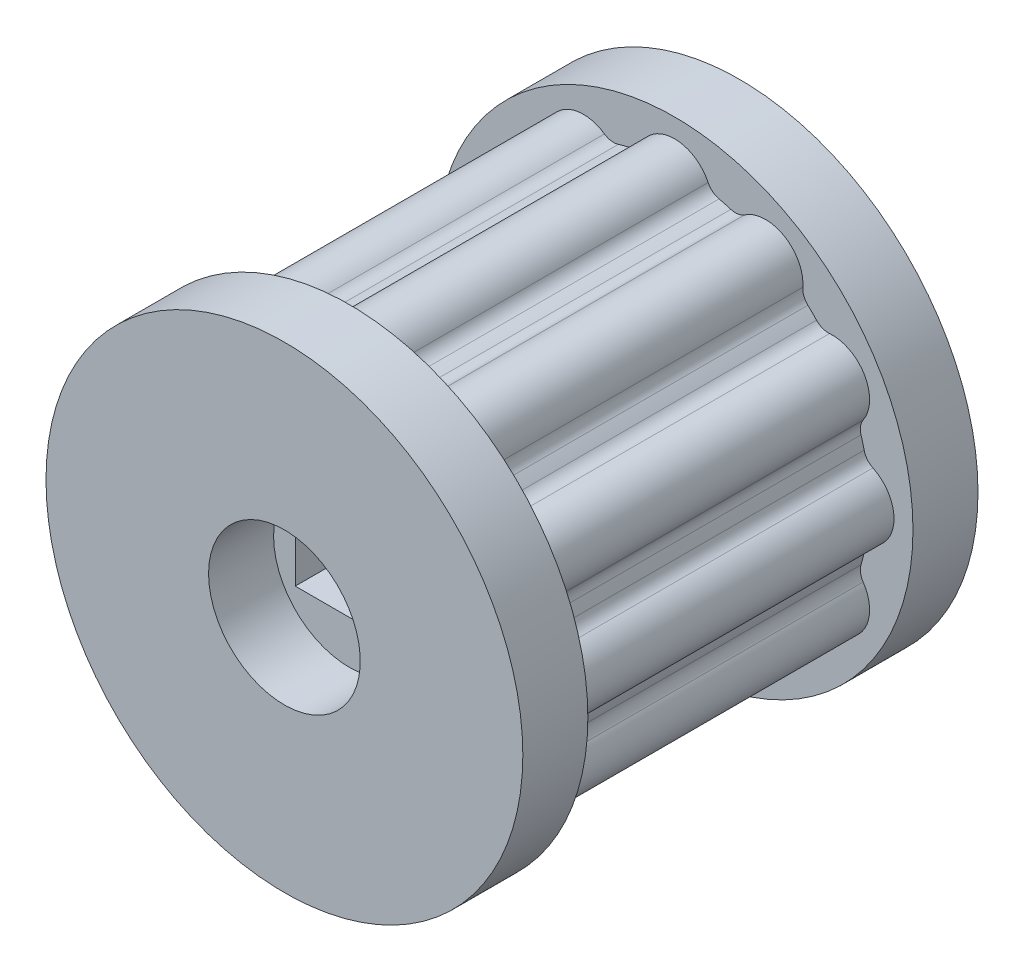
SolidWorks part; units mm, degrees
ref_plane "Plan de face" through (0, 0, 0) normal (0, 0, 1) x (1, 0, 0)
ref_plane "Plan de dessus" through (0, 0, 0) normal (0, 1, 0) x (1, 0, 0)
ref_plane "Plan de droite" through (0, 0, 0) normal (1, 0, 0) x (0, 0, -1)
sketch "Esquisse1" plane through (0, 0, 0) normal (0, 0, 1) x (1, 0, 0)
  line L0 (-2.5, 1.5) -> (2.5, 1.5)
  line L1 (-2.5, 1.5) -> (-2.5, -1.5)
  line L2 (-2.5, -1.5) -> (2.5, -1.5)
  line L3 (2.5, 1.5) -> (2.5, -1.5)
  circle A0 centre (0, 0) radius 11
  circle A1 centre (0, 0) radius 3.5
  point P7 (0, 1.5)
  point P8 (-2.5, 0)
  dimension "D1" = 22
  dimension "D2" = 5
  dimension "D3" = 3
extrude "Boss.-Extru.1" add sketch "Esquisse1" along normal blind 21 contours A0 A1 region at (-10.6889, 0, 0)
sketch "Esquisse2" plane through (0, 0, 0) normal (1, 0, 0) x (0, 0, -1)
  line L0 (0, 0) -> (-44, 0) construction
  line L1 (0, 0) -> (-22, 0)
  line L2 (-22, 0) -> (-22, 3.5)
  line L4 (-22, 3.5) -> (0, 3.5)
  line L6 (0, 3.5) -> (0, 0)
  dimension "D1" = 0
  dimension "D2" = 3.5
revolve "Enlèvement de matière-Révolution1" [suppressed] cut sketch "Esquisse2" angle 360 about L0
ref_plane "Plan1" through (0, 0, 3) normal (0, 0, -1) x (-1, 0, 0)
sketch "Esquisse3" plane through (0, 0, 3) normal (0, 0, -1) x (-1, 0, 0)
  circle A0 centre (0, 0) radius 8.985
  circle A1 centre (0, 0) radius 28.5
  dimension "D1" = 17.97
extrude "Enlèv. mat.-Extru.1" cut sketch "Esquisse3" against normal blind 15
sketch "Esquisse5" plane through (0, 0, 3) normal (0, 0, 1) x (1, 0, 0)
  line L0 (0, 0) -> (0, 38.7923) construction
  line L1 (0, 38.7923) -> (-15.821, 8.985) construction
  line L2 (-15.821, 8.985) -> (15.2424, 8.985) construction
  line L3 (-3.2223, 10.125) -> (3.5661, 10.125) construction
  circle A0 centre (0, 0) radius 8.985 construction
  arc A1 (-1.6667, 8.8291) -> (1.6667, 8.8291) centre (0, 0) cw
  arc A2 (-1.6667, 8.8291) -> (1.6667, 8.8291) centre (0, 8.4053) cw
  dimension "D1" = 1.14
  dimension "D2" = 1.6667
extrude "Boss.-Extru.2" add sketch "Esquisse5" along normal up to surface (15 mm away) up to face at (-8.985, 0, 18)
fillet "Congé1" radius 0.75 2 edges at (1.6667, 8.8291, 10.5) (-1.6667, 8.8291, 10.5)
pattern_circular "Répétition circulaire1" count 12 over 360 about axis through (0, 0, 3) along (0, 0, -1) of "Congé1", "Boss.-Extru.2"
extrude "Boss-Extrude1" add sketch "Esquisse1<3>" along normal mid plane 15 from offset 10.5 contours A1 L0 L3 L2 L1 region at (-3.401, 0, 0)
sketch "Esquisse1<3>" plane through (0, 0, 0) normal (0, 0, 1) x (1, 0, 0) same geometry as "Esquisse1"
